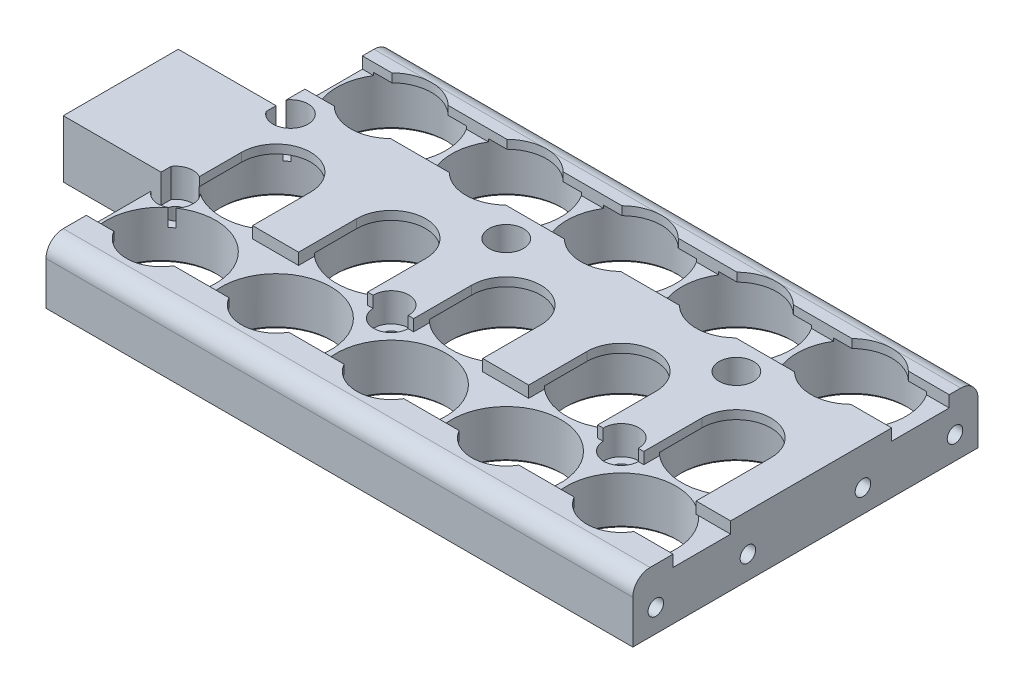
SolidWorks part; units mm, degrees
ref_plane "Front Plane" through (0, 0, 0) normal (0, 0, 1) x (1, 0, 0)
ref_plane "Top Plane" through (0, 0, 0) normal (0, 1, 0) x (1, 0, 0)
ref_plane "Right Plane" through (0, 0, 0) normal (1, 0, 0) x (0, 0, -1)
sketch "Sketch1" plane through (0, 0, 0) normal (0, 1, 0) x (1, 0, 0)
  line L0 (-48.3182, 0) -> (75.8679, 0)
  line L1 (-38.6124, 30) -> (61.3876, 30)
  line L2 (-38.6124, 30) -> (-38.6124, -30)
  line L3 (-38.6124, -30) -> (61.3876, -30)
  line L4 (61.3876, 30) -> (61.3876, -30)
  circle A0 centre (-28.6124, 20) radius 9.5
  circle A1 centre (-8.6124, 20) radius 9.5
  circle A2 centre (11.3876, 20) radius 9.5
  circle A3 centre (31.3876, 20) radius 9.5
  circle A4 centre (51.3876, 20) radius 9.5
  circle A5 centre (-28.6124, 0) radius 9.5
  circle A6 centre (-8.6124, 0) radius 9.5
  circle A7 centre (11.3876, 0) radius 9.5
  circle A8 centre (31.3876, 0) radius 9.5
  circle A9 centre (51.3876, 0) radius 9.5
  circle A10 centre (51.3876, -20) radius 9.5
  circle A11 centre (31.3876, -20) radius 9.5
  circle A12 centre (11.3876, -20) radius 9.5
  circle A13 centre (-8.6124, -20) radius 9.5
  circle A14 centre (-28.6124, -20) radius 9.5
  dimension "D3" = 19
  dimension "D4" = 19
  dimension "D5" = 19
  dimension "D6" = 19
  dimension "D7" = 19
  dimension "D8" = 20
  dimension "D9" = 20
  dimension "D10" = 20
  dimension "D11" = 20
  dimension "D12" = 10
  dimension "D13" = 10
  dimension "D14" = 20
  dimension "D15" = 20
  dimension "D16" = 20
  dimension "D17" = 20
  dimension "D18" = 20
  dimension "D19" = 10
  dimension "D20" = 20
  dimension "D21" = 20
  dimension "D22" = 20
  dimension "D23" = 20
  dimension "D25" = 30
  dimension "D26" = 19
  dimension "D27" = 19
  dimension "D28" = 19
  dimension "D29" = 19
  dimension "D30" = 19
  dimension "D1" = 60
  dimension "D2" = 100
  dimension "D24" = 10
extrude "Boss-Extrude1" add sketch "Sketch1" along normal blind 10 contours A9 L0 A8 A7 A6 A5 L2 L3 L4 A13 A11 A10 A12 A14 | A9 L0 L4 L1 L2 A5 A6 A7 A8 A4 A3 A2 A1 A0 region at (-37.5683, 0, -15) region at (-38.3624, 0, 1.044)
sketch "Sketch2" plane through (0, 10, 0) normal (0, 1, 0) x (1, 0, 0)
  line L1 (-38.6124, 30) -> (61.3876, 30)
  line L2 (-38.6124, 30) -> (-38.6124, -30)
  line L3 (-38.6124, -30) -> (61.3876, -30)
  line L4 (61.3876, 30) -> (61.3876, -30)
extrude "Boss-Extrude2" add sketch "Sketch2" against normal blind 1.5
sketch "Sketch3" plane through (0, 10, 0) normal (0, 1, 0) x (1, 0, 0)
  line L0 (-28.6124, 0) -> (-28.6124, -20) construction
  line L1 (-22.6124, 0) -> (-22.6124, -20)
  line L2 (-34.6124, 0) -> (-34.6124, -20)
  line L3 (-8.6124, 0) -> (-8.6124, -20) construction
  line L4 (-2.6124, 0) -> (-2.6124, -20)
  line L5 (-14.6124, 0) -> (-14.6124, -20)
  line L6 (11.3876, 34.8884) -> (11.3876, -40.3884)
  line L7 (61.3876, 30) -> (61.3876, -30) construction
  line L8 (31.3876, 0) -> (31.3876, -20) construction
  line L9 (25.3876, 0) -> (25.3876, -20)
  line L10 (37.3876, 0) -> (37.3876, -20)
  line L11 (51.3876, 0) -> (51.3876, -20) construction
  line L12 (45.3876, 0) -> (45.3876, -20)
  line L13 (57.3876, 0) -> (57.3876, -20)
  line L14 (11.3876, 0) -> (11.3876, -20) construction
  line L15 (17.3876, 0) -> (17.3876, -20)
  line L16 (5.3876, 0) -> (5.3876, -20)
  arc A0 (-22.6124, 0) -> (-34.6124, 0) centre (-28.6124, 0) ccw
  arc A1 (-34.6124, -20) -> (-22.6124, -20) centre (-28.6124, -20) ccw
  circle A2 centre (-28.6124, -20) radius 9.5 construction
  arc A3 (-2.6124, 0) -> (-14.6124, 0) centre (-8.6124, 0) ccw
  arc A4 (-14.6124, -20) -> (-2.6124, -20) centre (-8.6124, -20) ccw
  arc A5 (25.3876, 0) -> (37.3876, 0) centre (31.3876, 0) cw
  arc A6 (37.3876, -20) -> (25.3876, -20) centre (31.3876, -20) cw
  arc A7 (45.3876, 0) -> (57.3876, 0) centre (51.3876, 0) cw
  arc A8 (57.3876, -20) -> (45.3876, -20) centre (51.3876, -20) cw
  arc A9 (17.3876, 0) -> (5.3876, 0) centre (11.3876, 0) ccw
  arc A10 (5.3876, -20) -> (17.3876, -20) centre (11.3876, -20) ccw
  point P3 (-28.6124, -10)
  point P10 (-22.6124, -10)
  point P14 (-8.6124, -10)
  point P25 (31.3876, -10)
  point P32 (51.3876, -10)
  point P39 (11.3876, -10)
  dimension "D1" = 12
  dimension "D2" = 12
  dimension "D3" = 50
  dimension "D4" = 12
extrude "Cut-Extrude1" cut sketch "Sketch3" against normal blind 1.5 contours L5 A4 L4 A3 | L2 A1 L1 A0 | L6 A10 L15 A9 | L16 A10 L6 A9 | A8 L13 A7 L12 | A6 L10 A5 L9 region at (-28.6124, 10, 10) region at (-8.6124, 10, 10) region at (14.2424, 10, 10) region at (8.5329, 10, 10) region at (31.3876, 10, 10) region at (51.3876, 10, 10)
sketch "Sketch4" plane through (0, 10, 0) normal (0, 1, 0) x (1, 0, 0)
  line L1 (-46.445, -13) -> (66.265, -13)
  line L2 (-46.445, -13) -> (-46.445, -23)
  line L3 (-46.445, -23) -> (66.265, -23)
  line L4 (66.265, -13) -> (66.265, -23)
  arc A1 (-22.6124, -12.6345) -> (-34.6124, -12.6345) centre (-28.6124, -20) ccw construction
  arc A2 (-34.6124, -7.3655) -> (-22.6124, -7.3655) centre (-28.6124, 0) ccw construction
  dimension "D2" = 3
  dimension "D1" = 10
  dimension "D3" = 13
extrude "Cut-Extrude2" cut sketch "Sketch4" against normal blind 1.5
sketch "Sketch5" plane through (0, 10, 0) normal (0, 1, 0) x (1, 0, 0)
  line L1 (-43.2435, 25) -> (67.4964, 25)
  line L2 (-43.2435, 25) -> (-43.2435, 15)
  line L3 (-43.2435, 15) -> (67.4964, 15)
  line L4 (67.4964, 25) -> (67.4964, 15)
  line L6 (-38.6124, 30) -> (61.3876, 30) construction
  dimension "D1" = 10
  dimension "D2" = 5
extrude "Cut-Extrude4" cut sketch "Sketch5" against normal blind 1.5
sketch "Sketch6" plane through (0, 10, 0) normal (0, 1, 0) x (1, 0, 0)
  line L0 (-33.8085, -23) -> (-38.6124, -23) construction
  line L1 (-38.6124, -23) -> (-38.6124, -30) construction
  line L2 (-38.6124, -30) -> (61.3876, -30) construction
  line L3 (61.3876, -30) -> (61.3876, -23) construction
  line L4 (61.3876, -23) -> (56.5838, -23) construction
  line L5 (46.1915, -23) -> (36.5838, -23) construction
  line L6 (26.1915, -23) -> (16.5838, -23) construction
  line L7 (6.1915, -23) -> (-3.4162, -23) construction
  line L8 (-13.8085, -23) -> (-23.4162, -23) construction
  line L9 (-38.6124, 25) -> (61.3876, 25) construction
  line L10 (61.3876, 25) -> (61.3876, 30) construction
  line L11 (61.3876, 30) -> (-38.6124, 30) construction
  line L12 (-38.6124, 30) -> (-38.6124, 25) construction
  line L13 (61.3876, 15) -> (-38.6124, 15) construction
  line L14 (-38.6124, 15) -> (-38.6124, -13) construction
  line L15 (-38.6124, -13) -> (-34.6124, -13) construction
  line L16 (-34.6124, -13) -> (-34.6124, 0) construction
  line L17 (-22.6124, 0) -> (-22.6124, -13) construction
  line L18 (-22.6124, -13) -> (-14.6124, -13) construction
  line L19 (-14.6124, -13) -> (-14.6124, 0) construction
  line L20 (-2.6124, 0) -> (-2.6124, -13) construction
  line L21 (-2.6124, -13) -> (5.3876, -13) construction
  line L22 (5.3876, -13) -> (5.3876, 0) construction
  line L23 (17.3876, 0) -> (17.3876, -13) construction
  line L24 (17.3876, -13) -> (25.3876, -13) construction
  line L25 (25.3876, -13) -> (25.3876, 0) construction
  line L26 (37.3876, 0) -> (37.3876, -13) construction
  line L27 (37.3876, -13) -> (45.3876, -13) construction
  line L28 (45.3876, -13) -> (45.3876, 0) construction
  line L29 (57.3876, 0) -> (57.3876, -13) construction
  line L30 (57.3876, -13) -> (61.3876, -13) construction
  line L31 (61.3876, -13) -> (61.3876, 15) construction
  line L32 (-33.8085, -23) -> (-38.6124, -23)
  line L33 (-38.6124, -23) -> (-38.6124, -30)
  line L34 (-38.6124, -30) -> (61.3876, -30)
  line L35 (61.3876, -30) -> (61.3876, -23)
  line L36 (61.3876, -23) -> (56.5838, -23)
  line L37 (46.1915, -23) -> (36.5838, -23)
  line L38 (26.1915, -23) -> (16.5838, -23)
  line L39 (6.1915, -23) -> (-3.4162, -23)
  line L40 (-13.8085, -23) -> (-23.4162, -23)
  line L41 (-38.6124, 25) -> (61.3876, 25)
  line L42 (61.3876, 25) -> (61.3876, 30)
  line L43 (61.3876, 30) -> (-38.6124, 30)
  line L44 (-38.6124, 30) -> (-38.6124, 25)
  line L45 (61.3876, 15) -> (-38.6124, 15)
  line L46 (-38.6124, 15) -> (-38.6124, -13)
  line L47 (-38.6124, -13) -> (-34.6124, -13)
  line L48 (-34.6124, -13) -> (-34.6124, 0)
  line L49 (-22.6124, 0) -> (-22.6124, -13)
  line L50 (-22.6124, -13) -> (-14.6124, -13)
  line L51 (-14.6124, -13) -> (-14.6124, 0)
  line L52 (-2.6124, 0) -> (-2.6124, -13)
  line L53 (-2.6124, -13) -> (5.3876, -13)
  line L54 (5.3876, -13) -> (5.3876, 0)
  line L55 (17.3876, 0) -> (17.3876, -13)
  line L56 (17.3876, -13) -> (25.3876, -13)
  line L57 (25.3876, -13) -> (25.3876, 0)
  line L58 (37.3876, 0) -> (37.3876, -13)
  line L59 (37.3876, -13) -> (45.3876, -13)
  line L60 (45.3876, -13) -> (45.3876, 0)
  line L61 (57.3876, 0) -> (57.3876, -13)
  line L62 (57.3876, -13) -> (61.3876, -13)
  line L63 (61.3876, -13) -> (61.3876, 15)
  arc A0 (46.1915, -23) -> (56.5838, -23) centre (51.3876, -20) ccw construction
  arc A1 (26.1915, -23) -> (36.5838, -23) centre (31.3876, -20) ccw construction
  arc A2 (6.1915, -23) -> (16.5838, -23) centre (11.3876, -20) ccw construction
  arc A3 (-13.8085, -23) -> (-3.4162, -23) centre (-8.6124, -20) ccw construction
  arc A4 (-33.8085, -23) -> (-23.4162, -23) centre (-28.6124, -20) ccw construction
  arc A5 (-22.6124, 0) -> (-34.6124, 0) centre (-28.6124, 0) ccw construction
  arc A6 (-2.6124, 0) -> (-14.6124, 0) centre (-8.6124, 0) ccw construction
  arc A7 (17.3876, 0) -> (5.3876, 0) centre (11.3876, 0) ccw construction
  arc A8 (37.3876, 0) -> (25.3876, 0) centre (31.3876, 0) ccw construction
  arc A9 (57.3876, 0) -> (45.3876, 0) centre (51.3876, 0) ccw construction
  arc A10 (46.1915, -23) -> (56.5838, -23) centre (51.3876, -20) ccw
  arc A11 (26.1915, -23) -> (36.5838, -23) centre (31.3876, -20) ccw
  arc A12 (6.1915, -23) -> (16.5838, -23) centre (11.3876, -20) ccw
  arc A13 (-13.8085, -23) -> (-3.4162, -23) centre (-8.6124, -20) ccw
  arc A14 (-33.8085, -23) -> (-23.4162, -23) centre (-28.6124, -20) ccw
  arc A15 (-22.6124, 0) -> (-34.6124, 0) centre (-28.6124, 0) ccw
  arc A16 (-2.6124, 0) -> (-14.6124, 0) centre (-8.6124, 0) ccw
  arc A17 (17.3876, 0) -> (5.3876, 0) centre (11.3876, 0) ccw
  arc A18 (37.3876, 0) -> (25.3876, 0) centre (31.3876, 0) ccw
  arc A19 (57.3876, 0) -> (45.3876, 0) centre (51.3876, 0) ccw
extrude "Boss-Extrude3" add sketch "Sketch6" along normal blind 0.5
sketch "Sketch7" plane through (0, 10.5, 0) normal (0, 1, 0) x (1, 0, 0)
  line L0 (11.3876, 37.1048) -> (11.3876, 4.5971)
  circle A0 centre (-28.6124, 20) radius 7
  arc A1 (-20.5346, 15) -> (-20.5346, 25) centre (-28.6124, 20) ccw construction
  circle A2 centre (-8.6124, 20) radius 7
  circle A3 centre (11.3876, 20) radius 7
  arc A4 (-0.5346, 15) -> (-0.5346, 25) centre (-8.6124, 20) ccw construction
  circle A5 centre (31.3876, 20) radius 7
  circle A6 centre (51.3876, 20) radius 7
  dimension "D1" = 14
  dimension "D2" = 14
  dimension "D3" = 14
extrude "Cut-Extrude5" cut sketch "Sketch7" against normal blind 10 contours A0 | A2 | A3 | A5 | A6
sketch "Sketch8" plane through (0, 10.5, 0) normal (0, 1, 0) x (1, 0, 0)
  line L0 (61.3876, 30) -> (-38.6124, 30) construction
  line L1 (-38.6124, -30) -> (61.3876, -30) construction
  line L2 (-38.6124, 15) -> (-38.6124, -13) construction
  circle A0 centre (-36.1124, 10) radius 1.55
  circle A1 centre (-36.1124, -10) radius 1.55
  dimension "D1" = 20
  dimension "D2" = 20
  dimension "D3" = 3.1
  dimension "D4" = 2.5
  dimension "D5" = 2.5
  dimension "D6" = 3.1
extrude "Cut-Extrude6" cut sketch "Sketch8" against normal blind 21
sketch "Sketch9" plane through (0, 10.5, 0) normal (0, 1, 0) x (1, 0, 0)
  line L0 (-38.6124, -30) -> (61.3876, -30) construction
  line L1 (61.3876, 30) -> (-38.6124, 30) construction
  line L2 (-38.6124, 15) -> (-38.6124, -13) construction
  line L3 (-38.6124, -13) -> (-38.6124, -23) construction
  line L4 (21.3876, 36.4481) -> (21.3876, -38.2541)
  line L5 (61.3876, -13) -> (61.3876, 15) construction
  circle A0 centre (1.3876, 10) radius 1.55
  circle A1 centre (1.3876, -10) radius 1.55
  circle A2 centre (41.3876, -10) radius 1.55
  circle A3 centre (41.3876, 10) radius 1.55
  dimension "D1" = 20
  dimension "D2" = 20
  dimension "D3" = 3.1
  dimension "D4" = 3.1
  dimension "D5" = 40
  dimension "D6" = 40
  dimension "D7" = 74.7022
  dimension "D8" = 40
extrude "Cut-Extrude7" cut sketch "Sketch9" against normal blind 21 contours A0 | A1 | A3 | A2 region at (1.3876, 10.5, -10) region at (1.3876, 10.5, 10) region at (41.3876, 10.5, 10) region at (41.3876, 10.5, -10)
sketch "Sketch10" plane through (0, 10.5, 0) normal (0, 1, 0) x (1, 0, 0)
  circle A0 centre (-36.1124, 10) radius 3.05
  circle A1 centre (-36.1124, -10) radius 3.05
  circle A2 centre (1.3876, 10) radius 3
  circle A3 centre (1.3876, -10) radius 3.05
  circle A4 centre (41.3876, 10) radius 3
  circle A5 centre (41.3876, -10) radius 3.05
  dimension "D1" = 6.1
  dimension "D2" = 6
  dimension "D3" = 6
  dimension "D4" = 6.1
  dimension "D5" = 6.1
  dimension "D6" = 6.1
extrude "Cut-Extrude9" cut sketch "Sketch10" against normal blind 5
sketch "Sketch11" plane through (0, 8.5, 0) normal (0, 1, 0) x (1, 0, 0)
  line L1 (-43.9002, -10.0971) -> (49.929, -10.0971)
  line L2 (-43.9002, -10.0971) -> (-43.9002, -15.9255)
  line L3 (-43.9002, -15.9255) -> (49.929, -15.9255)
  line L4 (49.929, -10.0971) -> (49.929, -15.9255)
extrude "Cut-Extrude11" cut sketch "Sketch11" along normal blind 5
chamfer "Chamfer1" distance 0.5 angle 45 15 edges at (31.3876, 0, -10.5) (51.3876, 0, -10.5) (51.3876, 0, 9.5) (51.3876, 0, 29.5) (31.3876, 0, 29.5) (31.3876, 0, 9.5) (11.3876, 0, -10.5) (11.3876, 0, 29.5) (11.3876, 0, 9.5) (-8.6124, 0, 9.5) (-8.6124, 0, 29.5) (-28.6124, 0, 29.5) (-28.6124, 0, 9.5) (-8.6124, 0, -10.5) (-28.6124, 0, -10.5)
sketch "Sketch12" plane through (-38.6124, 0, 0) normal (-1, 0, 0) x (0, 0, 1)
  line L0 (-30, 0) -> (-20, 0) construction
  line L1 (14.5373, -0.4437) -> (9.5373, -0.4437)
  line L2 (14.5373, -0.4437) -> (14.5373, 2)
  line L3 (14.5373, 2) -> (9.5373, 2)
  line L4 (9.5373, -0.4437) -> (9.5373, 2)
  line L5 (0, -11.2928) -> (0, 14.9676)
  line L7 (-14.5373, 2) -> (-9.5373, 2)
  line L8 (-9.5373, -0.4437) -> (-9.5373, 2)
  line L9 (-14.5373, -0.4437) -> (-9.5373, -0.4437)
  line L10 (-14.5373, -0.4437) -> (-14.5373, 2)
  dimension "D1" = 2
  dimension "D2" = 5
extrude "Boss-Extrude4" add sketch "Sketch12" along normal blind 1.4 contours L4 L3 L2 L1 | L10 L7 L8 L9
sketch "Sketch13" plane through (-40.0124, 0, 0) normal (-1, 0, 0) x (0, 0, 1)
  line L1 (-14.5373, 2) -> (-9.5349, 2)
  line L2 (-14.5373, 2) -> (-14.5373, -2.7102)
  line L3 (-14.5373, -2.7102) -> (-9.5349, -2.7102)
  line L4 (-9.5349, 2) -> (-9.5349, -2.7102)
  line L5 (9.5373, 2) -> (14.5325, 2)
  line L6 (9.5373, 2) -> (9.5373, -2.7102)
  line L7 (9.5373, -2.7102) -> (14.5325, -2.7102)
  line L8 (14.5325, 2) -> (14.5325, -2.7102)
extrude "Boss-Extrude5" add sketch "Sketch13" along normal blind 2
sketch "Sketch14" plane through (-38.6124, 0, 0) normal (-1, 0, 0) x (0, 0, 1)
  line L0 (-6.95, 10.5) -> (-13.05, 10.5) construction
  line L1 (-10, 10.5) -> (10, 10.5)
  line L2 (-10, 10.5) -> (-10, 8)
  line L3 (-10, 8) -> (10, 8)
  line L4 (10, 10.5) -> (10, 8)
  dimension "D1" = 2.5
  dimension "D2" = 20
extrude "Boss-Extrude6" add sketch "Sketch14" along normal blind 10
sketch "Sketch15" plane through (-48.6124, 0, 0) normal (-1, 0, 0) x (0, 0, 1)
  line L4 (-10, 10.5) -> (-10, 8)
  line L5 (-10, 8) -> (10, 8)
  line L6 (10, 8) -> (10, 10.5)
  line L7 (10, 10.5) -> (-10, 10.5)
  line L8 (-10, 10.5) -> (-10, 8)
  line L9 (-10, 8) -> (10, 8)
  line L10 (10, 8) -> (10, 10.5)
  line L11 (10, 10.5) -> (-10, 10.5)
  dimension "D1" = 0
extrude "Boss-Extrude7" add sketch "Sketch15" along normal blind 7
sketch "Sketch16" plane through (-55.6124, 0, 0) normal (-1, 0, 0) x (0, 0, 1)
  line L0 (-6.95, 10.5) -> (-13.05, 10.5) construction
  line L1 (-10, 10.5) -> (-7.95, 10.5)
  line L2 (-10, 10.5) -> (-10, 0.5)
  line L3 (-10, 0.5) -> (-7.95, 0.5)
  line L4 (-7.95, 10.5) -> (-7.95, 0.5)
  line L5 (10, 10.5) -> (-10, 10.5) construction
  line L6 (10, 10.5) -> (7.95, 10.5)
  line L7 (10, 10.5) -> (10, 0.5)
  line L8 (10, 0.5) -> (7.95, 0.5)
  line L9 (7.95, 10.5) -> (7.95, 0.5)
  point P11 (8.975, 0.5)
  dimension "D1" = 15.9
  dimension "D2" = 2.05
  dimension "D3" = 2.05
  dimension "D4" = 10
  dimension "D5" = 10
extrude "Boss-Extrude8" add sketch "Sketch16" against normal up to surface (17 mm away) up to face at (-38.6124, 4.931, -1.1724)
chamfer "Chamfer2" distance 2.5 angle 45 1 edges at (-47.1124, 8, 7.95)
chamfer "Chamfer3" distance 2 angle 45 3 edges at (-38.6124, 3, 7.95) (-38.6124, 4.25, -7.95) (-38.6124, 8, -1.25)
fillet "Fillet1" radius 3 2 edges at (11.3876, 10.5, 30) (11.3876, 10.5, -30)
sketch "Sketch17" plane through (61.3876, 0, 0) normal (1, 0, 0) x (0, 0, -1)
  line L15 (-23, 10.5) -> (-27, 10.5)
  line L16 (-30, 7.5) -> (-30, 0)
  line L17 (-30, 0) -> (-20, 0)
  line L18 (-20, 0) -> (0, 0)
  line L19 (0, 0) -> (20, 0)
  line L20 (20, 0) -> (30, 0)
  line L21 (30, 0) -> (30, 7.5)
  line L22 (27, 10.5) -> (25, 10.5)
  line L23 (25, 10.5) -> (25, 8.5)
  line L24 (25, 8.5) -> (15, 8.5)
  line L25 (15, 8.5) -> (15, 10.5)
  line L26 (15, 10.5) -> (-13, 10.5)
  line L27 (-13, 10.5) -> (-13, 8.5)
  line L28 (-13, 8.5) -> (-23, 8.5)
  line L29 (-23, 8.5) -> (-23, 10.5)
  line L30 (-23, 10.5) -> (-27, 10.5)
  line L31 (-30, 7.5) -> (-30, 0)
  line L32 (-30, 0) -> (-20, 0)
  line L33 (-20, 0) -> (0, 0)
  line L34 (0, 0) -> (20, 0)
  line L35 (20, 0) -> (30, 0)
  line L36 (30, 0) -> (30, 7.5)
  line L37 (27, 10.5) -> (25, 10.5)
  line L38 (25, 10.5) -> (25, 8.5)
  line L39 (25, 8.5) -> (15, 8.5)
  line L40 (15, 8.5) -> (15, 10.5)
  line L41 (15, 10.5) -> (-13, 10.5)
  line L42 (-13, 10.5) -> (-13, 8.5)
  line L43 (-13, 8.5) -> (-23, 8.5)
  line L44 (-23, 8.5) -> (-23, 10.5)
  arc A2 (-27, 10.5) -> (-30, 7.5) centre (-27, 7.5) ccw
  arc A3 (30, 7.5) -> (27, 10.5) centre (27, 7.5) ccw
  arc A4 (-27, 10.5) -> (-30, 7.5) centre (-27, 7.5) ccw
  arc A5 (30, 7.5) -> (27, 10.5) centre (27, 7.5) ccw
  dimension "D1" = 0
extrude "Boss-Extrude9" add sketch "Sketch17" along normal blind 2
sketch "Sketch18" plane through (63.3876, 0, 0) normal (1, 0, 0) x (0, 0, -1)
  line L0 (30, 0) -> (30, 7.5) construction
  line L1 (-30, 0) -> (30, 0) construction
  line L2 (0, 20.2965) -> (0, -9.256)
  circle A0 centre (10, 4) radius 1.35
  circle A1 centre (26, 4) radius 1.35
  circle A2 centre (-26, 4) radius 1.35
  circle A3 centre (-10, 4) radius 1.35
  dimension "D1" = 4
  dimension "D2" = 2.7
  dimension "D3" = 2.7
  dimension "D4" = 4
  dimension "D5" = 4
  dimension "D6" = 20
extrude "Cut-Extrude12" cut sketch "Sketch18" against normal blind 3 contours A2 | A3 | A0 | A1 region at (63.3876, 4, 26) region at (63.3876, 4, 10)
sketch "Sketch19" plane through (0, 8.5, 0) normal (0, -1, 0) x (1, 0, 0)
  line L0 (46.4886, -25) -> (43.3099, -25) construction
  line L1 (59.4654, -25) -> (56.2866, -25) construction
  line L2 (56.2866, -15) -> (59.4654, -15) construction
  line L3 (43.3099, -15) -> (46.4886, -15) construction
  line L4 (26.4886, -25) -> (23.3099, -25) construction
  line L5 (39.4654, -25) -> (36.2866, -25) construction
  line L6 (36.2866, -15) -> (39.4654, -15) construction
  line L7 (23.3099, -15) -> (26.4886, -15) construction
  line L8 (19.4654, -25) -> (16.2866, -25) construction
  line L9 (6.4886, -25) -> (3.3099, -25) construction
  line L10 (3.3099, -15) -> (6.4886, -15) construction
  line L11 (16.2866, -15) -> (19.4654, -15) construction
  line L12 (-0.5346, -25) -> (-3.7134, -25) construction
  line L13 (-13.5114, -25) -> (-16.6901, -25) construction
  line L14 (-16.6901, -15) -> (-13.5114, -15) construction
  line L15 (-3.7134, -15) -> (-0.5346, -15) construction
  line L16 (-36.6901, -15) -> (-33.5114, -15) construction
  line L17 (-23.7134, -15) -> (-20.5346, -15) construction
  line L18 (-20.5346, -25) -> (-23.7134, -25) construction
  line L19 (-33.5114, -25) -> (-36.6901, -25) construction
  line L20 (-34.6124, 0) -> (-34.6124, 7.3443) construction
  line L21 (-22.6124, 7.3655) -> (-22.6124, 0) construction
  line L22 (-14.6124, 0) -> (-14.6124, 7.3655) construction
  line L23 (-2.6124, 7.3655) -> (-2.6124, 0) construction
  line L24 (17.3876, 7.3655) -> (17.3876, 0) construction
  line L25 (5.3876, 0) -> (5.3876, 7.3655) construction
  line L26 (25.3876, 0) -> (25.3876, 7.3655) construction
  line L27 (37.3876, 7.3655) -> (37.3876, 0) construction
  line L28 (45.3876, 0) -> (45.3876, 7.3655) construction
  line L29 (57.3876, 7.3655) -> (57.3876, 0) construction
  line L30 (42.3737, 23) -> (46.1915, 23) construction
  line L31 (56.5838, 23) -> (60.4015, 23) construction
  line L32 (22.3737, 23) -> (26.1915, 23) construction
  line L33 (36.5838, 23) -> (40.4015, 23) construction
  line L34 (2.3737, 23) -> (6.1915, 23) construction
  line L35 (16.5838, 23) -> (20.4015, 23) construction
  line L36 (-37.6263, 23) -> (-33.8085, 23) construction
  line L37 (-23.4162, 23) -> (-19.5985, 23) construction
  line L38 (-17.6263, 23) -> (-13.8085, 23) construction
  line L39 (-3.4162, 23) -> (0.4015, 23) construction
  line L40 (46.4886, -25) -> (43.3099, -25)
  line L41 (59.4654, -25) -> (56.2866, -25)
  line L42 (56.2866, -15) -> (59.4654, -15)
  line L43 (43.3099, -15) -> (46.4886, -15)
  line L44 (26.4886, -25) -> (23.3099, -25)
  line L45 (39.4654, -25) -> (36.2866, -25)
  line L46 (36.2866, -15) -> (39.4654, -15)
  line L47 (23.3099, -15) -> (26.4886, -15)
  line L48 (19.4654, -25) -> (16.2866, -25)
  line L49 (6.4886, -25) -> (3.3099, -25)
  line L50 (3.3099, -15) -> (6.4886, -15)
  line L51 (16.2866, -15) -> (19.4654, -15)
  line L52 (-0.5346, -25) -> (-3.7134, -25)
  line L53 (-13.5114, -25) -> (-16.6901, -25)
  line L54 (-16.6901, -15) -> (-13.5114, -15)
  line L55 (-3.7134, -15) -> (-0.5346, -15)
  line L56 (-36.6901, -15) -> (-33.5114, -15)
  line L57 (-23.7134, -15) -> (-20.5346, -15)
  line L58 (-20.5346, -25) -> (-23.7134, -25)
  line L59 (-33.5114, -25) -> (-36.6901, -25)
  line L60 (-34.6124, 0) -> (-34.6124, 7.3443)
  line L61 (-22.6124, 7.3655) -> (-22.6124, 0)
  line L62 (-14.6124, 0) -> (-14.6124, 7.3655)
  line L63 (-2.6124, 7.3655) -> (-2.6124, 0)
  line L64 (17.3876, 7.3655) -> (17.3876, 0)
  line L65 (5.3876, 0) -> (5.3876, 7.3655)
  line L66 (25.3876, 0) -> (25.3876, 7.3655)
  line L67 (37.3876, 7.3655) -> (37.3876, 0)
  line L68 (45.3876, 0) -> (45.3876, 7.3655)
  line L69 (57.3876, 7.3655) -> (57.3876, 0)
  line L70 (42.3737, 23) -> (46.1915, 23)
  line L71 (56.5838, 23) -> (60.4015, 23)
  line L72 (22.3737, 23) -> (26.1915, 23)
  line L73 (36.5838, 23) -> (40.4015, 23)
  line L74 (2.3737, 23) -> (6.1915, 23)
  line L75 (16.5838, 23) -> (20.4015, 23)
  line L76 (-37.6263, 23) -> (-33.8085, 23)
  line L77 (-23.4162, 23) -> (-19.5985, 23)
  line L78 (-17.6263, 23) -> (-13.8085, 23)
  line L79 (-3.4162, 23) -> (0.4015, 23)
  arc A0 (46.4886, -25) -> (56.2866, -25) centre (51.3876, -20) ccw construction
  arc A1 (43.3099, -25) -> (59.4654, -25) centre (51.3876, -20) ccw construction
  arc A2 (56.2866, -15) -> (46.4886, -15) centre (51.3876, -20) ccw construction
  arc A3 (59.4654, -15) -> (43.3099, -15) centre (51.3876, -20) ccw construction
  arc A4 (26.4886, -25) -> (36.2866, -25) centre (31.3876, -20) ccw construction
  arc A5 (23.3099, -25) -> (39.4654, -25) centre (31.3876, -20) ccw construction
  arc A6 (36.2866, -15) -> (26.4886, -15) centre (31.3876, -20) ccw construction
  arc A7 (39.4654, -15) -> (23.3099, -15) centre (31.3876, -20) ccw construction
  arc A8 (6.4886, -25) -> (16.2866, -25) centre (11.3876, -20) ccw construction
  arc A9 (3.3099, -25) -> (19.4654, -25) centre (11.3876, -20) ccw construction
  arc A10 (16.2866, -15) -> (6.4886, -15) centre (11.3876, -20) ccw construction
  arc A11 (19.4654, -15) -> (3.3099, -15) centre (11.3876, -20) ccw construction
  arc A12 (-13.5114, -25) -> (-3.7134, -25) centre (-8.6124, -20) ccw construction
  arc A13 (-16.6901, -25) -> (-0.5346, -25) centre (-8.6124, -20) ccw construction
  arc A14 (-3.7134, -15) -> (-13.5114, -15) centre (-8.6124, -20) ccw construction
  arc A15 (-0.5346, -15) -> (-16.6901, -15) centre (-8.6124, -20) ccw construction
  arc A16 (-20.5346, -15) -> (-33.9217, -12.1221) centre (-28.6124, -20) ccw construction
  arc A17 (-34.6886, -12.6973) -> (-33.9217, -12.1221) centre (-36.1124, -10) ccw construction
  arc A18 (-34.6886, -12.6973) -> (-36.6901, -15) centre (-28.6124, -20) ccw construction
  arc A19 (-23.7134, -15) -> (-33.5114, -15) centre (-28.6124, -20) ccw construction
  arc A20 (-33.5114, -25) -> (-23.7134, -25) centre (-28.6124, -20) ccw construction
  arc A21 (-36.6901, -25) -> (-20.5346, -25) centre (-28.6124, -20) ccw construction
  arc A22 (-34.6886, 7.3027) -> (-34.6124, 7.3443) centre (-36.1124, 10) ccw construction
  arc A23 (-34.6886, 7.3027) -> (-34.6886, -7.3027) centre (-28.6124, 0) ccw construction
  arc A24 (-33.9217, -7.8779) -> (-34.6886, -7.3027) centre (-36.1124, -10) ccw construction
  arc A25 (-33.9217, -7.8779) -> (-22.6124, 7.3655) centre (-28.6124, 0) ccw construction
  arc A26 (-34.6124, 0) -> (-22.6124, 0) centre (-28.6124, 0) ccw construction
  arc A27 (-14.6124, 0) -> (-2.6124, 0) centre (-8.6124, 0) ccw construction
  arc A28 (-14.6124, 7.3655) -> (-2.6124, 7.3655) centre (-8.6124, 0) ccw construction
  arc A29 (5.3876, 0) -> (17.3876, 0) centre (11.3876, 0) ccw construction
  arc A30 (5.3876, 7.3655) -> (17.3876, 7.3655) centre (11.3876, 0) ccw construction
  arc A31 (25.3876, 0) -> (37.3876, 0) centre (31.3876, 0) ccw construction
  arc A32 (25.3876, 7.3655) -> (37.3876, 7.3655) centre (31.3876, 0) ccw construction
  arc A33 (45.3876, 0) -> (57.3876, 0) centre (51.3876, 0) ccw construction
  arc A34 (45.3876, 7.3655) -> (57.3876, 7.3655) centre (51.3876, 0) ccw construction
  arc A35 (60.4015, 23) -> (42.3737, 23) centre (51.3876, 20) ccw construction
  arc A36 (56.5838, 23) -> (46.1915, 23) centre (51.3876, 20) ccw construction
  arc A37 (40.4015, 23) -> (22.3737, 23) centre (31.3876, 20) ccw construction
  arc A38 (36.5838, 23) -> (26.1915, 23) centre (31.3876, 20) ccw construction
  arc A39 (20.4015, 23) -> (2.3737, 23) centre (11.3876, 20) ccw construction
  arc A40 (16.5838, 23) -> (6.1915, 23) centre (11.3876, 20) ccw construction
  arc A41 (-19.5985, 23) -> (-37.6263, 23) centre (-28.6124, 20) ccw construction
  arc A42 (-23.4162, 23) -> (-33.8085, 23) centre (-28.6124, 20) ccw construction
  arc A43 (0.4015, 23) -> (-17.6263, 23) centre (-8.6124, 20) ccw construction
  arc A44 (-3.4162, 23) -> (-13.8085, 23) centre (-8.6124, 20) ccw construction
  arc A45 (46.4886, -25) -> (56.2866, -25) centre (51.3876, -20) ccw
  arc A46 (43.3099, -25) -> (59.4654, -25) centre (51.3876, -20) ccw
  arc A47 (56.2866, -15) -> (46.4886, -15) centre (51.3876, -20) ccw
  arc A48 (59.4654, -15) -> (43.3099, -15) centre (51.3876, -20) ccw
  arc A49 (26.4886, -25) -> (36.2866, -25) centre (31.3876, -20) ccw
  arc A50 (23.3099, -25) -> (39.4654, -25) centre (31.3876, -20) ccw
  arc A51 (36.2866, -15) -> (26.4886, -15) centre (31.3876, -20) ccw
  arc A52 (39.4654, -15) -> (23.3099, -15) centre (31.3876, -20) ccw
  arc A53 (6.4886, -25) -> (16.2866, -25) centre (11.3876, -20) ccw
  arc A54 (3.3099, -25) -> (19.4654, -25) centre (11.3876, -20) ccw
  arc A55 (16.2866, -15) -> (6.4886, -15) centre (11.3876, -20) ccw
  arc A56 (19.4654, -15) -> (3.3099, -15) centre (11.3876, -20) ccw
  arc A57 (-13.5114, -25) -> (-3.7134, -25) centre (-8.6124, -20) ccw
  arc A58 (-16.6901, -25) -> (-0.5346, -25) centre (-8.6124, -20) ccw
  arc A59 (-3.7134, -15) -> (-13.5114, -15) centre (-8.6124, -20) ccw
  arc A60 (-0.5346, -15) -> (-16.6901, -15) centre (-8.6124, -20) ccw
  arc A61 (-20.5346, -15) -> (-33.9217, -12.1221) centre (-28.6124, -20) ccw
  arc A62 (-34.6886, -12.6973) -> (-33.9217, -12.1221) centre (-36.1124, -10) ccw
  arc A63 (-34.6886, -12.6973) -> (-36.6901, -15) centre (-28.6124, -20) ccw
  arc A64 (-23.7134, -15) -> (-33.5114, -15) centre (-28.6124, -20) ccw
  arc A65 (-33.5114, -25) -> (-23.7134, -25) centre (-28.6124, -20) ccw
  arc A66 (-36.6901, -25) -> (-20.5346, -25) centre (-28.6124, -20) ccw
  arc A67 (-34.6886, 7.3027) -> (-34.6124, 7.3443) centre (-36.1124, 10) ccw
  arc A68 (-34.6886, 7.3027) -> (-34.6886, -7.3027) centre (-28.6124, 0) ccw
  arc A69 (-33.9217, -7.8779) -> (-34.6886, -7.3027) centre (-36.1124, -10) ccw
  arc A70 (-33.9217, -7.8779) -> (-22.6124, 7.3655) centre (-28.6124, 0) ccw
  arc A71 (-34.6124, 0) -> (-22.6124, 0) centre (-28.6124, 0) ccw
  arc A72 (-14.6124, 0) -> (-2.6124, 0) centre (-8.6124, 0) ccw
  arc A73 (-14.6124, 7.3655) -> (-2.6124, 7.3655) centre (-8.6124, 0) ccw
  arc A74 (5.3876, 0) -> (17.3876, 0) centre (11.3876, 0) ccw
  arc A75 (5.3876, 7.3655) -> (17.3876, 7.3655) centre (11.3876, 0) ccw
  arc A76 (25.3876, 0) -> (37.3876, 0) centre (31.3876, 0) ccw
  arc A77 (25.3876, 7.3655) -> (37.3876, 7.3655) centre (31.3876, 0) ccw
  arc A78 (45.3876, 0) -> (57.3876, 0) centre (51.3876, 0) ccw
  arc A79 (45.3876, 7.3655) -> (57.3876, 7.3655) centre (51.3876, 0) ccw
  arc A80 (60.4015, 23) -> (42.3737, 23) centre (51.3876, 20) ccw
  arc A81 (56.5838, 23) -> (46.1915, 23) centre (51.3876, 20) ccw
  arc A82 (40.4015, 23) -> (22.3737, 23) centre (31.3876, 20) ccw
  arc A83 (36.5838, 23) -> (26.1915, 23) centre (31.3876, 20) ccw
  arc A84 (20.4015, 23) -> (2.3737, 23) centre (11.3876, 20) ccw
  arc A85 (16.5838, 23) -> (6.1915, 23) centre (11.3876, 20) ccw
  arc A86 (-19.5985, 23) -> (-37.6263, 23) centre (-28.6124, 20) ccw
  arc A87 (-23.4162, 23) -> (-33.8085, 23) centre (-28.6124, 20) ccw
  arc A88 (0.4015, 23) -> (-17.6263, 23) centre (-8.6124, 20) ccw
  arc A89 (-3.4162, 23) -> (-13.8085, 23) centre (-8.6124, 20) ccw
extrude "Cut-Extrude13" cut sketch "Sketch19" against normal blind 0.5
